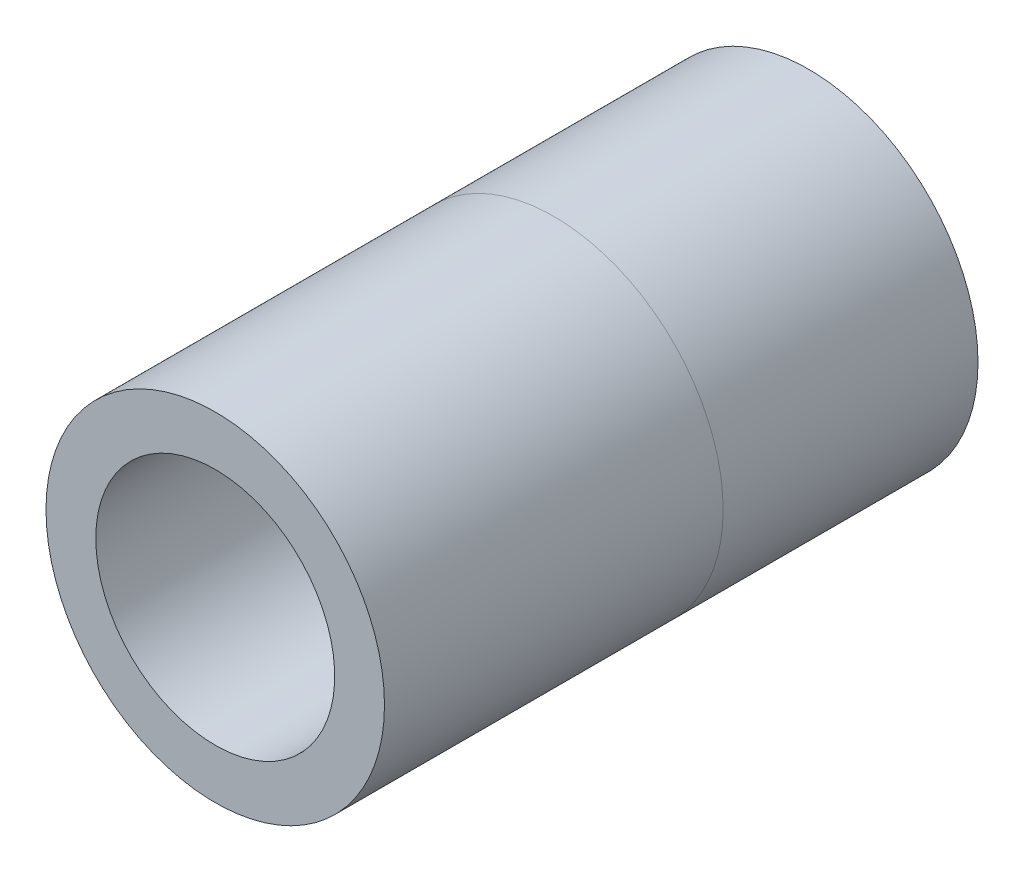
SolidWorks part; units mm, degrees
material "Silicon Rubber"
ref_plane "X-Y Datum" through (0, 0, 0) normal (0, 0, 1) x (1, 0, 0)
ref_plane "X-Z Datum" through (0, 0, 0) normal (0, 1, 0) x (1, 0, 0)
ref_plane "Y-Z Datum" through (0, 0, 0) normal (1, 0, 0) x (0, 0, -1)
sketch3d "3DSketch1"
  line L0 (-90.1376, 20.5421, 0) -> (-90.1376, 20.5421, -20.32)
  line L1 (-90.1376, 20.5421, 4) -> (-90.1376, 20.5421, 0) construction
  line L2 (-90.1376, 20.5421, 0) -> (-90.1376, 20.5421, 27)
  circle A0 centre (-90.1376, 20.5421, 0) radius 9.1798 construction
  arc A1 (-87.2578, 27.597, -20.32) -> (-93.0143, 13.4859, -20.32) centre (-90.1376, 20.5421, -20.32) ccw construction
  circle A2 centre (-90.1376, 20.5421, 27) radius 10 construction
  point P6 (-90.1376, 20.5421, 9.1798)
  point P10 (-90.1376, 20.5421, -12.7)
  point P14 (-90.1376, 20.5421, 17)
sweep "Sweep1" add path "3DSketch1" circular profile diameter 26.9875 parameters "D3"=26.9875
sweep "Cut-Sweep1" cut path "3DSketch1<2>" circular profile diameter 19.05 parameters "D3"=19.05
sketch3d "3DSketch1<2>" same geometry as "3DSketch1"
